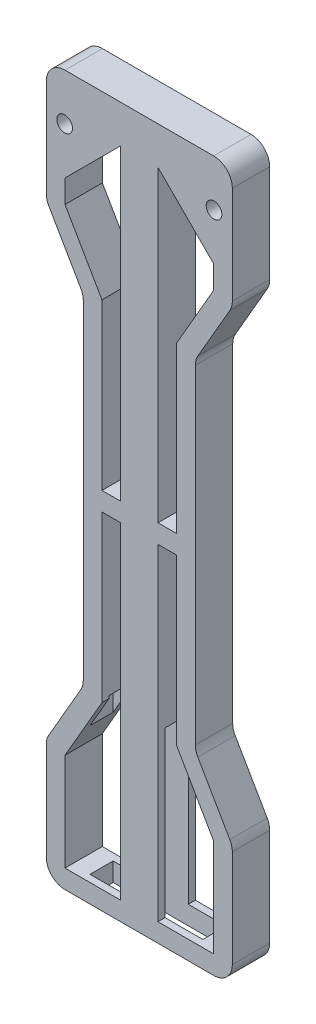
SolidWorks part; units mm, degrees
ref_plane "前视基准面" through (0, 0, 0) normal (0, 0, 1) x (1, 0, 0)
ref_plane "上视基准面" through (0, 0, 0) normal (0, 1, 0) x (1, 0, 0)
ref_plane "右视基准面" through (0, 0, 0) normal (1, 0, 0) x (0, 0, -1)
other "Configuration Table"
sketch "草图1" plane through (0, 0, 0) normal (0, 0, 1) x (1, 0, 0)
  line L1 (-24.9, 95) -> (24.9, 95)
  line L2 (-24.9, 95) -> (-24.9, -95)
  line L3 (-24.9, -95) -> (24.9, -95)
  line L4 (24.9, 95) -> (24.9, -95)
  line L5 (-24.9, 95) -> (24.9, -95) construction
  line L6 (-24.9, -95) -> (24.9, 95) construction
  point P0 (0, 0)
  dimension "D1" = 49.8
  dimension "D2" = 190
extrude "凸台-拉伸1" add sketch "草图1" along normal mid plane 10
sketch "草图3" plane through (0, -95, 0) normal (0, -1, 0) x (1, 0, 0)
  line L1 (-15.1, 3.1) -> (15.1, 3.1)
  line L2 (-15.1, 3.1) -> (-15.1, -3.1)
  line L3 (-15.1, -3.1) -> (15.1, -3.1)
  line L4 (15.1, 3.1) -> (15.1, -3.1)
  line L5 (-15.1, 3.1) -> (15.1, -3.1) construction
  line L6 (-15.1, -3.1) -> (15.1, 3.1) construction
  point P0 (0, 0)
  dimension "D1" = 6.2
  dimension "D2" = 30.2
sketch "草图4" plane through (0, 0, -5) normal (0, 0, -1) x (-1, 0, 0)
  line L0 (-24.9, 62.5) -> (-15, 45.3527)
  line L1 (-24.9, -95) -> (-24.9, 95) construction
  line L2 (-15, 45.3527) -> (-15, -45.3527)
  line L3 (-15, -45.3527) -> (-24.9, -62.5)
  line L4 (-24.9, -62.5) -> (-24.9, 62.5)
  line L5 (0, 0) -> (0, 82.1988) construction
  line L6 (24.9, -62.5) -> (24.9, 62.5)
  line L7 (15, -45.3527) -> (24.9, -62.5)
  line L8 (15, 45.3527) -> (15, -45.3527)
  line L9 (24.9, 62.5) -> (15, 45.3527)
  point P7 (-15, 0)
  point P11 (-24.9, 0)
  dimension "D1" = 125
  dimension "D2" = 15
  dimension "D3" = 30
extrude "切除-拉伸1" cut sketch "草图4" against normal through all
fillet "圆角1" radius 5 12 edges at (15, -45.3527, 0) (24.9, -62.5, 0) (24.9, -95, 0) (-24.9, -95, 0) (-24.9, -62.5, 0) (-15, -45.3527, 0) (-15, 45.3527, 0) (-24.9, 62.5, 0) (24.9, 62.5, 0) (15, 45.3527, 0) (-24.9, 95, 0) (24.9, 95, 0)
sketch "草图5" plane through (0, 0, -5) normal (0, 0, -1) x (-1, 0, 0)
  line L0 (-19.9, 90) -> (-19.9, 63.8397)
  line L1 (-19.9, 63.8397) -> (-10, 46.6924)
  line L2 (-10, 46.6924) -> (-10, 2.5)
  line L3 (-10, 2.5) -> (-5, 2.5)
  line L4 (-5, 2.5) -> (-5, 90)
  line L5 (-5, 90) -> (-19.9, 90)
  line L6 (0, 0) -> (52.13, 0) construction
  line L7 (-19.9, 95) -> (19.9, 95) construction
  line L8 (-15.6699, 46.513) -> (-24.2301, 61.3397) construction
  line L9 (-24.9, 63.8397) -> (-24.9, 90) construction
  line L10 (-15, -44.013) -> (-15, 44.013) construction
  line L11 (0, -23.1926) -> (0, 23.1926) construction
  line L12 (5, 90) -> (19.9, 90)
  line L13 (5, 2.5) -> (5, 90)
  line L14 (10, 2.5) -> (5, 2.5)
  line L15 (10, 46.6924) -> (10, 2.5)
  line L16 (19.9, 63.8397) -> (10, 46.6924)
  line L17 (19.9, 90) -> (19.9, 63.8397)
  line L18 (19.9, -90) -> (19.9, -63.8397)
  line L19 (19.9, -63.8397) -> (10, -46.6924)
  line L20 (10, -46.6924) -> (10, -2.5)
  line L21 (10, -2.5) -> (5, -2.5)
  line L22 (5, -2.5) -> (5, -90)
  line L23 (5, -90) -> (19.9, -90)
  line L24 (-5, -90) -> (-19.9, -90)
  line L25 (-5, -2.5) -> (-5, -90)
  line L26 (-10, -2.5) -> (-5, -2.5)
  line L27 (-10, -46.6924) -> (-10, -2.5)
  line L28 (-19.9, -63.8397) -> (-10, -46.6924)
  line L29 (-19.9, -90) -> (-19.9, -63.8397)
  point P15 (-24.9, 76.9199)
  dimension "D1" = 5
  dimension "D2" = 5
  dimension "D3" = 5
  dimension "D4" = 5
  dimension "D5" = 5
  dimension "D6" = 5
extrude "切除-拉伸2" cut sketch "草图5" against normal through all
chamfer "倒角2" distance 20 angle 45 2 edges at (-19.9, 90, 0) (19.9, 90, 0)
sketch "草图7" plane through (0, 0, -5) normal (0, 0, -1) x (-1, 0, 0)
  line L0 (0, 0) -> (0, 106.6084) construction
  line L1 (-19.9, 95) -> (19.9, 95) construction
  circle A0 centre (-20, 82.5) radius 2.1
  circle A1 centre (20, 82.5) radius 2.1
  dimension "D1" = 4.2
  dimension "D3" = 12.5
  dimension "D2" = 40
extrude "切除-拉伸6" cut sketch "草图7" against normal up to next
extrude "切除-拉伸7" cut sketch "草图3" against normal blind 49
chamfer "倒角3" distance 5 angle 45 2 edges at (15.1, -46, 0) (-15.1, -46, 0)
sketch "草图9" plane through (0, 0, -5) normal (0, 0, -1) x (-1, 0, 0)
  circle A0 centre (-20, 82.5) radius 3.7
  circle A1 centre (20, 82.5) radius 3.7
  dimension "D1" = 7.4
extrude "切除-拉伸8" cut sketch "草图9" against normal blind 5
